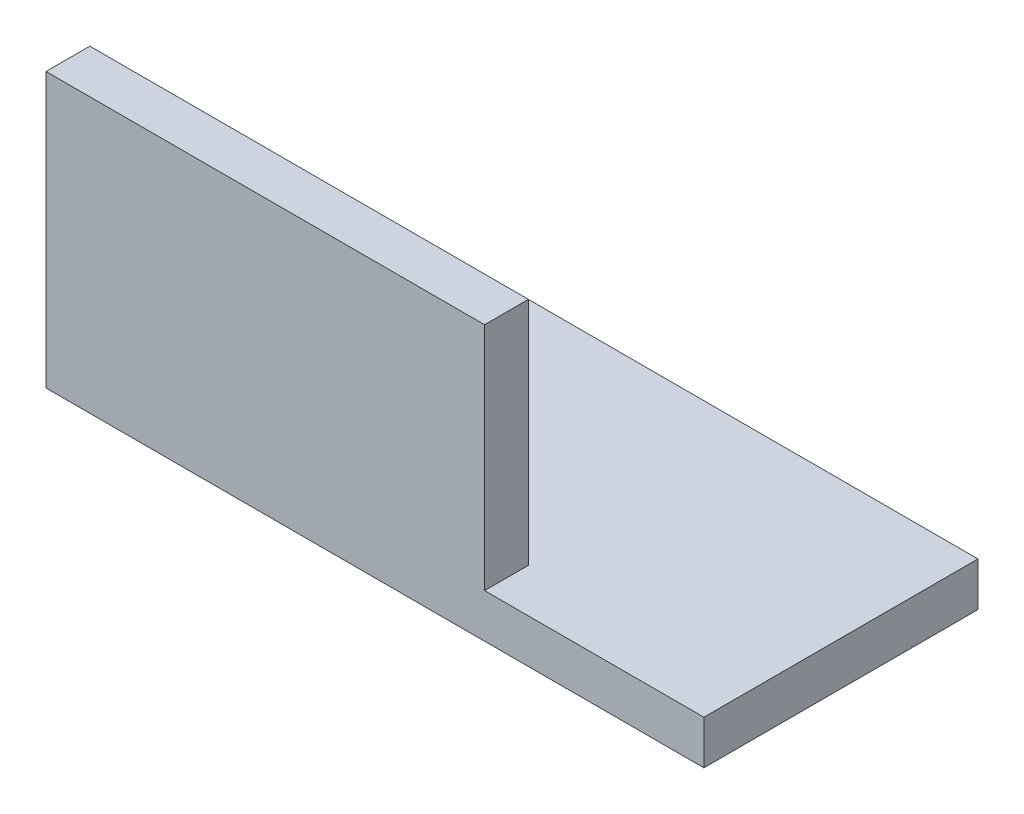
SolidWorks part; units mm, degrees
ref_plane "Спереди" through (0, 0, 0) normal (0, 0, 1) x (1, 0, 0)
ref_plane "Сверху" through (0, 0, 0) normal (0, 1, 0) x (1, 0, 0)
ref_plane "Справа" through (0, 0, 0) normal (1, 0, 0) x (0, 0, -1)
sketch "Эскиз1" plane through (0, 0, 0) normal (1, 0, 0) x (0, 0, -1)
  line L0 (0, 0) -> (25, 0)
  line L1 (0, 0) -> (0, 25)
extrude "Вытянуть-Тонкостенный1" add sketch "Эскиз1" along normal blind 60 thin thin type one direction wall 4
sketch "Эскиз2" plane through (0, 0, 0) normal (0, 0, 1) x (1, 0, 0)
  line L0 (60, 0) -> (60, 25) construction
  line L1 (40, 25) -> (60, 25)
  line L2 (40, 25) -> (40, 4)
  line L3 (40, 4) -> (60, 4)
  line L4 (60, 25) -> (60, 4)
  line L5 (60, 25) -> (0, 25) construction
extrude "Вырез-Вытянуть1" cut sketch "Эскиз2" against normal through all
